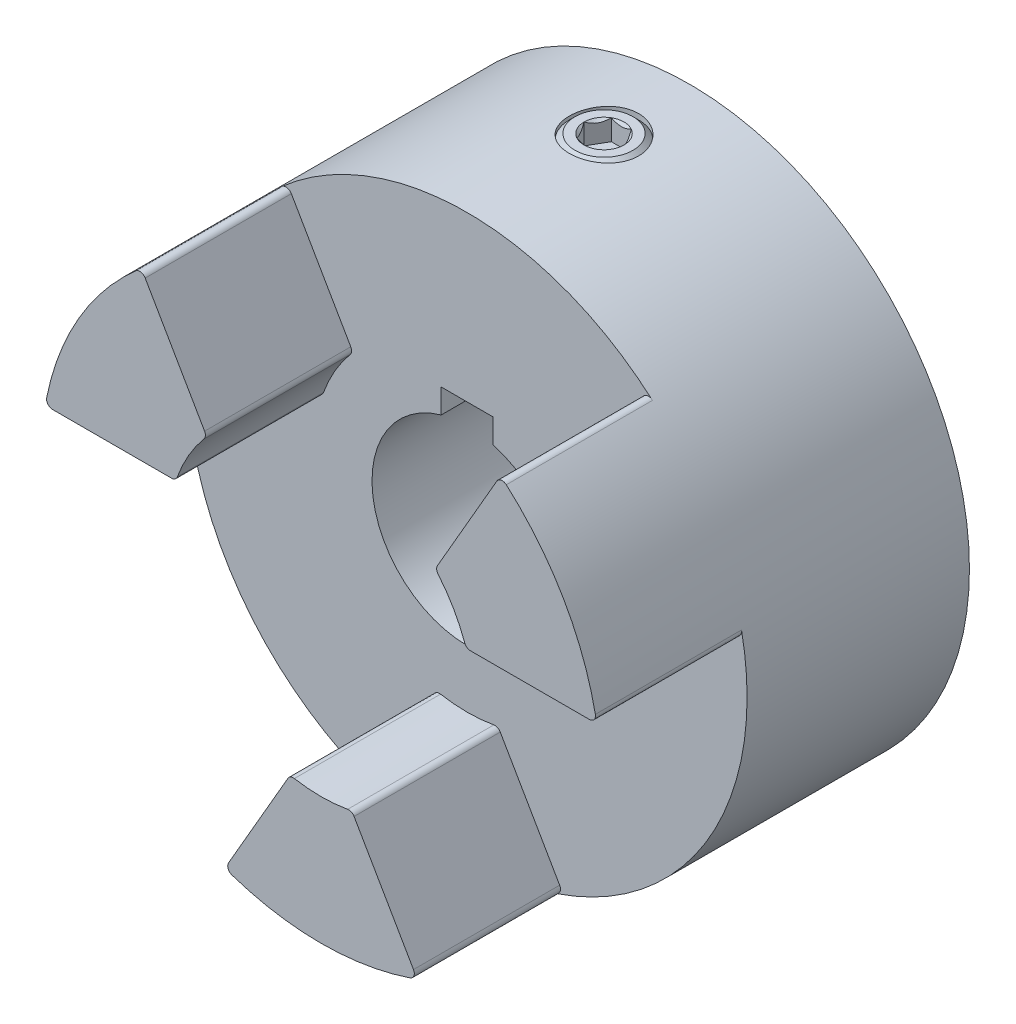
SolidWorks part; units mm, degrees
ref_plane "Front" through (0, 0, 0) normal (0, 0, 1) x (1, 0, 0)
ref_plane "Top" through (0, 0, 0) normal (0, 1, 0) x (1, 0, 0)
ref_plane "Right" through (0, 0, 0) normal (1, 0, 0) x (0, 0, -1)
sketch "Sketch3" plane through (0, 0, 0) normal (1, 0, 0) x (0, 0, -1)
  line L0 (36.1156, 0) -> (-36.1156, 0) construction
  circle A0 centre (0, 0) radius 7.7629 construction
  circle A1 centre (0, 0) radius 11 construction
  circle A2 centre (0, 0) radius 32.3453 construction
  point P7 (0, 7.7629)
  point P8 (0, -7.7629)
  point P9 (0, 11)
  point P10 (0, -11)
  point P11 (0, 32.3453)
  point P12 (0, -32.3453)
  point P13 (9.1281, 0)
  point P14 (-7.7629, 0)
  point P15 (7.7629, 0)
  point P16 (-7.7629, 32.3453)
  point P17 (36.1156, 32.3453)
  point P18 (9.1281, 32.3453)
  dimension "OD" = 64.6906
  dimension "Shaft Dia" = 22
  dimension "Overall Lg" = 72.2313
  dimension "Bore Depth" = 26.9875
  dimension "Lug Lg" = 16.891
sketch "Sketch1" plane through (0, 0, 0) normal (0, 0, 1) x (1, 0, 0)
  circle A0 centre (0, 0) radius 32.3453
  circle A1 centre (0, 0) radius 11 construction
extrude "Boss-Extrude1" add sketch "Sketch1" against normal up to vertex (36.1156 mm away) from vertex up to point (0, 0, -36.1156) starting at point (0, 0, -9.1281)
sketch "Sketch10" [suppressed] plane through (0, 0, -3.5719) normal (0, 0, 1) x (1, 0, 0)
  arc A14 (-1.0963, -4.1108) -> (1.0963, -4.1108) centre (0, 0) ccw
  arc A15 (-3.4409, -7.1529) -> (-1.0963, -4.1108) centre (-9.5758, 0) ccw
  arc A19 (1.0963, -4.1108) -> (3.4409, -7.1529) centre (9.5758, 0) ccw
  circle A32 centre (0, 0) radius 7.9375 construction
  arc A33 (-3.4409, -7.1529) -> (3.4409, -7.1529) centre (0, 0) ccw
  point P0 (0, -4.2545)
  point P1 (0, -7.9375)
  dimension "D1" = 3.683
  dimension "D4" = 9.4234
  dimension "D2" = 6.8819
  dimension "D3" = 2.1926
extrude "Boss-Extrude4" [suppressed] add sketch "Sketch10" along normal up to vertex up to point (0, 0, 7.7629)
fillet "Fillet2" [suppressed] radius 0.381
other "Move Face3" [suppressed] parameters "D1"=90
pattern_circular "CirPattern2" [suppressed] count 2 over 360 of bodies 116
sketch "Sketch11" [suppressed] plane through (0, 0, -5.9531) normal (0, 0, 1) x (1, 0, 0)
  arc A0 (-1.5825, -7.8835) -> (1.5738, -7.8835) centre (-0.0044, -0.0397) ccw
  arc A1 (-1.5825, -7.8835) -> (-2.9616, -8.354) centre (-1.8681, -9.3029) ccw
  arc A2 (-2.9616, -8.354) -> (-4.9794, -11.8231) centre (5.1535, -15.3956) ccw
  arc A3 (-4.9794, -11.8231) -> (-4.4308, -12.9555) centre (-4.1442, -12.1175) ccw
  arc A4 (-4.4308, -12.9555) -> (4.4176, -12.96) centre (0, 0) ccw
  arc A5 (4.4176, -12.96) -> (4.9692, -11.8231) centre (4.1308, -12.1185) ccw
  arc A6 (4.9692, -11.8231) -> (2.9523, -8.354) centre (-5.1643, -15.3938) ccw
  arc A7 (2.9523, -8.354) -> (1.5738, -7.8835) centre (1.8592, -9.3021) ccw
  circle A8 centre (0, 0) radius 13.6922 construction
  point P18 (-0.007, -13.6922)
  point P19 (-0.0044, -8.0407)
  dimension "D1" = 1.4478
  dimension "D2" = 8.001
  dimension "D3" = 10.7442
  dimension "D4" = 0.889
  dimension "D9" = 5.6515
  dimension "D5" = 5.072
  dimension "D6" = 3.1563
  dimension "D7" = 5.9139
  dimension "D8" = 9.9486
extrude "Boss-Extrude5" [suppressed] add sketch "Sketch11" along normal up to vertex up to point (0, 0, 7.7629)
other "Move Face1" [suppressed] parameters "D1"=90
pattern_circular "CirPattern3" [suppressed] count 2 over 360 of bodies 118
sketch "Sketch12" [suppressed] plane through (0, 0, -6.1516) normal (0, 0, 1) x (1, 0, 0)
  line L0 (-5.1097, -10.267) -> (-8.533, -13.6894)
  line L1 (8.533, -13.6894) -> (5.1097, -10.267)
  arc A0 (-2.3442, -9.4968) -> (2.3442, -9.4968) centre (0, 0) ccw
  arc A1 (-2.3442, -9.4968) -> (-5.1097, -10.267) centre (-3.0443, -12.333) ccw
  arc A2 (-8.533, -13.6894) -> (-8.3299, -15.1215) centre (-7.8934, -14.3292) ccw
  arc A3 (-8.3299, -15.1215) -> (8.3299, -15.1215) centre (0, 0) ccw
  arc A4 (8.3299, -15.1215) -> (8.533, -13.6894) centre (7.8934, -14.3292) ccw
  arc A5 (5.1097, -10.267) -> (2.3442, -9.4968) centre (3.0443, -12.333) ccw
  circle A6 centre (0, 0) radius 17.2641 construction
  point P16 (0, -9.7819)
  point P17 (0, -17.2641)
  dimension "D1" = 7.4822
  dimension "D2" = 10.2193
  dimension "D3" = 4.6884
  dimension "D4" = 17.066
  dimension "D5" = 16.6598
extrude "Boss-Extrude6" [suppressed] add sketch "Sketch12" along normal up to vertex up to point (0, 0, 7.7629)
other "Move Face2" [suppressed] parameters "D1"=90
pattern_circular "CirPattern4" [suppressed] count 2 over 360 of bodies 120
sketch "Sketch2" plane through (0, 0, -9.1281) normal (0, 0, 1) x (1, 0, 0)
  line L0 (-11.1144, -30.3758) -> (-3.5662, -17.302)
  line L2 (3.5662, -17.302) -> (11.1144, -30.3758)
  circle A0 centre (0, 0) radius 32.3453 construction
  arc A1 (-11.1144, -30.3758) -> (11.1144, -30.3758) centre (0, 0) ccw
  arc A2 (-3.5662, -17.302) -> (3.5662, -17.302) centre (0, 0) ccw
  circle A3 centre (0, 0) radius 5.5626 construction
  dimension "Spider Inner body Dia" = 35.3314
  dimension "Spider Leg Thickness" = 11.1252
  dimension "D4" = 7.1324
  dimension "D1" = 60
extrude "Boss-Extrude2" add sketch "Sketch2" along normal up to vertex (16.891 mm away) up to point (0, 0, 7.7629)
fillet "Fillet1" radius 0.7132 4 edges at (3.5662, -17.302, -0.6826) (-3.5662, -17.302, -0.6826)
pattern_circular "CirPattern1" count 3 over 360 about axis through (0, 0, -36.1156) along (0, 0, 1) of "Boss-Extrude2", "Fillet1"
sketch "Sketch15" plane through (0, 0, 0) normal (0, 0, 1) x (1, 0, 0)
  circle A0 centre (0, 0) radius 11
extrude "Cut-Extrude5" cut sketch "Sketch15" against normal through all and the other way through all
chamfer "Chamfer1" distance 1.2938 angle 56 2 edges at (32.3453, 0, -36.1156) (11, 0, -36.1156) first distance on face at (32.3453, 0, -36.1156) first distance on face at (11, 0, -9.1281)
sketch "Sketch4" plane through (0, 0, 0) normal (0, 0, 1) x (1, 0, 0)
  line L1 (-3, 13.383) -> (3, 13.383)
  line L2 (-3, 13.383) -> (-3, 10.583)
  line L4 (3, 13.383) -> (3, 10.583)
  arc A1 (3, 10.583) -> (-3, 10.583) centre (0, 0) ccw
  circle A2 centre (0, 0) radius 11 construction
  dimension "Keyway Ht" = 2.8
  dimension "Keyway Wd" = 6
extrude "Cut-Extrude1" cut sketch "Sketch4" against normal through all and the other way through all
sketch "Sketch5" plane through (0, 0, 0) normal (0, 1, 0) x (1, 0, 0)
  line L1 (0, -46.4939) -> (0, 46.4939) construction
  circle A0 centre (0, 24.9396) radius 4
  dimension "Screw Dia" = 8
  dimension "Screw Offset" = 11.176
extrude "Cut-Extrude2" cut sketch "Sketch5" along normal through all
ref_plane "Plane1" through (0, 32.3453, 0) normal (0, 1, 0) x (-1, 0, 0)
sketch "Sketch6" plane through (0, 32.3453, 0) normal (0, 1, 0) x (-1, 0, 0)
  circle A1 centre (0, -24.9396) radius 4
  circle A2 centre (0, -24.9396) radius 4
  dimension "D1" = 0
extrude "Boss-Extrude3" add sketch "Sketch6" against normal blind 12 separate body
sketch "Sketch8" plane through (0, 32.3453, 0) normal (0, 1, 0) x (1, 0, 0)
  line L1 (1.1547, 22.9396) -> (2.3094, 24.9396)
  line L2 (2.3094, 24.9396) -> (1.1547, 26.9396)
  line L3 (1.1547, 26.9396) -> (-1.1547, 26.9396)
  line L4 (-1.1547, 26.9396) -> (-2.3094, 24.9396)
  line L5 (-2.3094, 24.9396) -> (-1.1547, 22.9396)
  line L6 (-1.1547, 22.9396) -> (1.1547, 22.9396)
  circle A0 centre (0, 24.9396) radius 2 construction
  dimension "D1" = 4
extrude "Cut-Extrude3" cut sketch "Sketch8" against normal blind 2.4
sketch "Sketch9" plane through (0, 32.3453, 0) normal (0, 1, 0) x (1, 0, 0)
  circle A0 centre (0, 24.9396) radius 2.3094
extrude "Cut-Extrude4" cut sketch "Sketch9" against normal through all draft 45
chamfer "Chamfer3" distance 0.64 angle 45 1 edges at (0, 32.3453, -20.9396)
chamfer "Chamfer4" distance 1.36 angle 45 1 edges at (0, 20.3453, -20.9396)
sketch "Sketch16" [suppressed] plane through (0, 0, -61.9125) normal (0, 0, -1) x (-1, 0, 0)
  circle A0 centre (0, 0) radius 50.8
  dimension "D1" = 101.6
extrude "Cut-Extrude6" [suppressed] cut sketch "Sketch16" against normal blind 30.3022 flip side to cut
chamfer "Chamfer5" [suppressed] distance 1.778 angle 56
fillet "Fillet3" [suppressed] radius 1.27
move or copy body "Body-Move/Copy1" [suppressed] bodies to move or copy 115 copy no translate (0, -6.35, 0)
sketch "Sketch17" [suppressed] plane through (0, 0, -67.8656) normal (0, 0, -1) x (-1, 0, 0)
  circle A0 centre (0, 0) radius 53.975
  dimension "D1" = 107.95
extrude "Cut-Extrude7" [suppressed] cut sketch "Sketch17" against normal blind 36.576 flip side to cut
move or copy body "Body-Move/Copy2" [suppressed] bodies to move or copy 115 copy no translate (0, -9.525, 0)
fillet "Fillet4" [suppressed] radius 2.54
fillet "Fillet5" [suppressed] radius 1.27
equation "\"D1@Chamfer1\" = \"OD@Sketch3\" * .02"
equation "\"D1@Fillet1\" = \"D4@Sketch2\" * .1"
equation "\"D1@Sketch8\" = \"Screw Dia@Sketch5\" * .5"
equation "\"D1@Cut-Extrude3\" = \"Screw Dia@Sketch5\" * .3"
equation "\"D1@Chamfer3\" = \"Screw Dia@Sketch5\" * .08"
equation "\"D1@Chamfer4\" = \"Screw Dia@Sketch5\" * .17"
